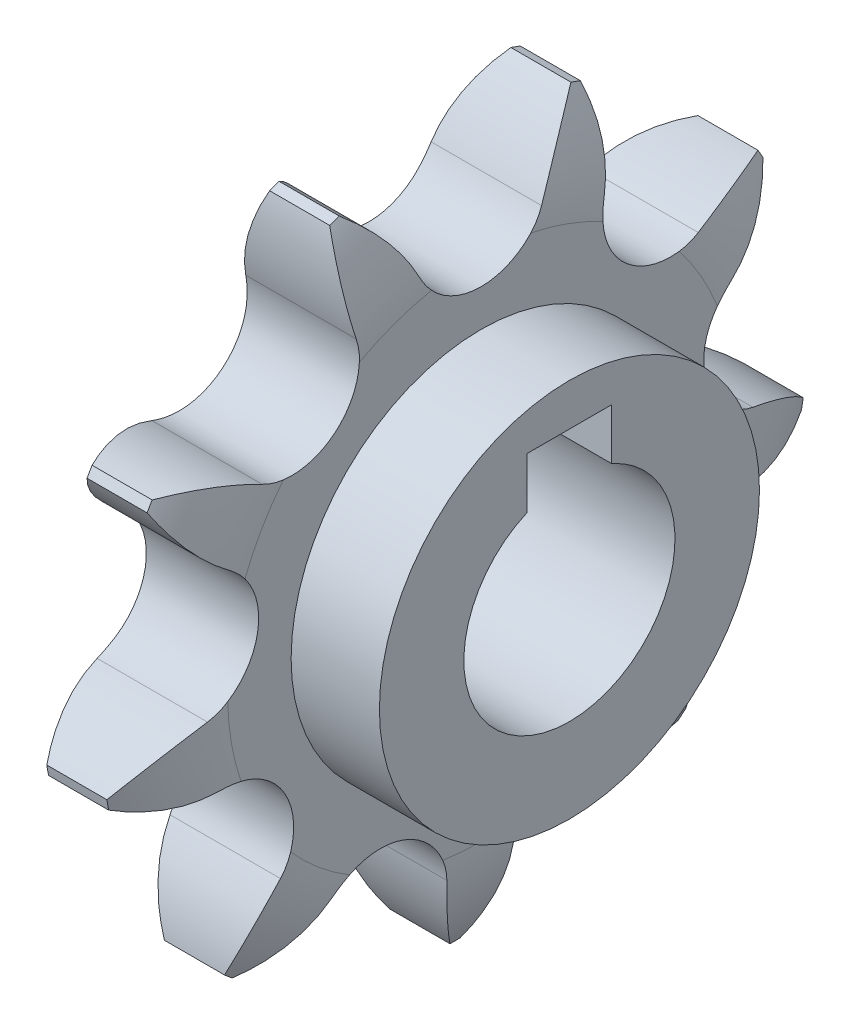
SolidWorks part; units mm, degrees
ref_plane "Plane1" through (0, 0, 0) normal (0, 0, 1) x (1, 0, 0)
ref_plane "Plane2" through (0, 0, 0) normal (0, 1, 0) x (1, 0, 0)
ref_plane "Plane3" through (0, 0, 0) normal (1, 0, 0) x (0, 0, -1)
sketch "Clipboard" plane through (0, 0, 0) normal (0, 1, 0) x (1, 0, 0)
  line L0 (0, 0) -> (9.4077, -1.49)
  line L1 (-15, 0) -> (100, 0) construction
  line L2 (0, 0) -> (-0.8203, 0.9272)
  line L3 (0, 0) -> (-8.8973, 3.4006)
  line L4 (0, 0) -> (3.0618, 0.4849)
  line L5 (0, 0) -> (-46.8476, -17.4728)
  line L6 (0, 0) -> (-4.4098, -2.9753)
  line L7 (-0.8203, 0.9272) -> (48.4205, 9.6097)
  line L8 (-76.2, 38.1) -> (-74.4, 38.1)
  line L9 (-73.3242, 40.7328) -> (-72.926, 40.7699)
  line L10 (-73.4529, 9.1872) -> (-63.2129, 9.1872)
  circle A0 centre (0, 0) radius 3.175
  circle A1 centre (0, 0) radius 8.4097
  circle A2 centre (0, 0) radius 37.5
  dimension "Num_teeth" = 9
  dimension "Thickness" = 5.3196
sketch "BasProSke" plane through (0, 0, 0) normal (0, 1, 0) x (1, 0, 0)
  line L0 (-10, 0) -> (60, 0) construction
  line L1 (0, 0) -> (0, 12.0069)
  line L2 (0, 0) -> (5.3196, 0)
  line L3 (5.3196, 0) -> (5.3196, 12.0069)
  line L4 (4.0816, 16.7027) -> (1.238, 16.7027)
  arc A0 (0, 12.0069) -> (1.238, 16.7027) centre (9.525, 12.0069) cw
  arc A1 (5.3196, 12.0069) -> (4.0816, 16.7027) centre (-4.2054, 12.0069) ccw
  dimension "D1" = 9.525
  dimension "Thickness" = 5.3196
  dimension "Diameter" = 33.4055
revolve "Base-Revolve" add sketch "BasProSke" angle 360 about L0
sketch "TooCutSke" plane through (0, 0, 0) normal (1, 0, 0) x (0, 0, -1)
  line L0 (0, 13.9564) -> (2.9063, 12.6011) construction
  line L1 (0, 0) -> (0, 107) construction
  line L2 (0, 13.9564) -> (-10, 13.9564) construction
  line L3 (0, 13.9564) -> (-2.9063, 12.6011) construction
  arc A0 (2.9063, 12.6011) -> (5.9941, 16.1247) centre (10.503, 9.0588) cw
  arc A1 (2.9063, 12.6011) -> (-2.9063, 12.6011) centre (0, 13.9564) cw
  arc A2 (-2.9063, 12.6011) -> (-5.9941, 16.1247) centre (-10.503, 9.0588) ccw
  arc A3 (5.9941, 16.1247) -> (-5.9941, 16.1247) centre (0, 0) ccw
extrude "ToothCut" cut sketch "TooCutSke" along normal through all
pattern_circular "TeethCuts" count 9 every 40 about axis through (-10, 0, 0) along (1, 0, 0) of "ToothCut"
sketch "HubNeaOneSke" plane through (0, 0, 0) normal (-1, 0, 0) x (0, 0, 1)
  circle A0 centre (0, 0) radius 8.4097
  dimension "Diameter" = 16.8193
extrude "HubNearOne" [suppressed] add sketch "HubNeaOneSke" along normal blind 44.6809
fillet "HubNearOneFillet" [suppressed] radius 0.4
sketch "HubNeaBotSke" plane through (0, 0, 0) normal (-1, 0, 0) x (0, 0, 1)
  circle A0 centre (0, 0) radius 8.4097
  dimension "Diameter" = 16.8193
extrude "HubNearBoth" [suppressed] add sketch "HubNeaBotSke" along normal blind 22.3405
fillet "HubNearBothFillet" [suppressed] radius 0.4
ref_plane "FarPln" through (5.3196, 0, 0) normal (1, 0, 0) x (0, 0, -1)
sketch "HubFarSke" plane through (5.3196, 0, 0) normal (1, 0, 0) x (0, 0, -1)
  circle A0 centre (0, 0) radius 8.4097
  dimension "Diameter" = 16.8193
extrude "HubFar" [suppressed] add sketch "HubFarSke" along normal blind 22.3405
fillet "HubFarFillet" [suppressed] radius 0.4
sketch "BorSke" plane through (0, 0, 0) normal (1, 0, 0) x (0, 0, -1)
  circle A0 centre (0, 0) radius 5
  dimension "Diameter" = 10
extrude "Bore" cut sketch "BorSke" along normal mid plane 100.001
sketch "KeySke" plane through (0, 0, 0) normal (1, 0, 0) x (0, 0, -1)
  line L0 (-2, 0) -> (-2, 6.8)
  line L1 (-2, 6.8) -> (2, 6.8)
  line L2 (2, 6.8) -> (2, 0)
  line L3 (0, 0) -> (0, 34) construction
  line L4 (-2, 0) -> (2, 0)
  dimension "Width" = 4
extrude "Keyway" [suppressed] cut sketch "KeySke" along normal mid plane 100.001
pattern_circular "Keyway2" [suppressed] count 2 every 90 about axis through (-10, 0, 0) along (1, 0, 0)
sketch "Sketch1" plane through (5.3196, 0, 0) normal (1, 0, 0) x (0, 0, -1)
  circle A0 centre (0, 0) radius 9
  circle A1 centre (0, 0) radius 3
  dimension "D1" = 18
  dimension "D2" = 6
extrude "Boss-Extrude1" add sketch "Sketch1" along normal offset from surface (16.6804 mm away) 22 up to face at (0, 0, -5)
sketch "Sketch2" plane through (0, 0, 0) normal (1, 0, 0) x (0, 0, -1)
  circle A0 centre (0, 0) radius 5
  dimension "D1" = 10
extrude "Cut-Extrude1" cut sketch "Sketch2" along normal blind 24
sketch "Sketch3" plane through (0, 0, 0) normal (-1, 0, 0) x (0, 0, 1)
  line L0 (-2, 7) -> (-2, 3)
  line L1 (-2, 7) -> (2, 7)
  line L2 (-2, 3) -> (2, 3)
  line L3 (2, 7) -> (2, 3)
  line L4 (-2, 7) -> (2, 3) construction
  line L5 (-2, 3) -> (2, 7) construction
  line L6 (0, 0) -> (0, 5) construction
  circle A0 centre (0, 0) radius 5 construction
  point P1 (0, 5)
  dimension "D1" = 4
  dimension "D2" = 4
extrude "Cut-Extrude2" cut sketch "Sketch3" against normal through all
sketch "Sketch4" plane through (22, 0, 0) normal (1, 0, 0) x (0, 0, -1)
  circle A0 centre (0, 0) radius 12.1759
extrude "Cut-Extrude3" cut sketch "Sketch4" against normal blind 12.5
equation "' \"Pitch@Clipboard\" = 12.7"
equation "' \"Num_strands@Clipboard\" = 1"
equation "' \"Num_teeth@Clipboard\" = 9"
equation "' \"Hub_dia@Clipboard\" = 50"
equation "' \"Overall_len@Clipboard\" = 3"
equation "' \"Diameter@BorSke\" = 12"
equation "' \"T_dim@Clipboard\" = 1"
equation "' \"Width@KeySke\" = 2"
equation "' \"Dr@Clipboard\" = 8.51"
equation "' \"Face_width@Clipboard\" = 7.2"
equation "' \"Side_radius@Clipboard\" = 12.7"
equation "' \"Side_relief@Clipboard\" = 1.27"
equation "' \"Transv_pitch@Clipboard\" = 13.92"
equation "' \"Show_teeth@Clipboard\" = 9"
equation "' \"Fillet_rad@Clipboard\" = 0.6"
equation "' \"Plate_wid@Clipboard\" = 11.8"
equation "\"Num_teeth@Clipboard\" = int( \"Num_teeth@Clipboard\" )"
equation "\"Num_teeth@Clipboard\" = ((sgn( \"Num_teeth@Clipboard\" - 5.0)+1)*( \"Num_teeth@Clipboard\" - 5.0))/2 +5.0"
equation "\"Num_teeth@Clipboard\" = ((sgn( \"Num_teeth@Clipboard\" - 200.0)-1)*( \"Num_teeth@Clipboard\" - 200.0))/-2 +200.0"
equation "\"MHD@Clipboard\" = \"Pitch@Clipboard\" * (1.0 / tan(3.14159265 / \"Num_teeth@Clipboard\" )) - 1.04 * \"Plate_wid@Clipboard\" - 0.76"
equation "\"Thickness@Clipboard\"  = \"Face_width@Clipboard\" + (\"Num_strands@Clipboard\" - 1) * \"Transv_pitch@Clipboard\""
equation "\"OAL@Clipboard\" = \"Thickness@Clipboard\" + 2 * \"Fillet_rad@Clipboard\" + 1"
equation "\"MHD@Clipboard\" = ((sgn( \"MHD@Clipboard\" - \"Hub_dia@Clipboard\" )-1)*( \"MHD@Clipboard\" - \"Hub_dia@Clipboard\" ))/-2+ \"Hub_dia@Clipboard\""
equation "\"OAL@Clipboard\" = ((sgn( \"OAL@Clipboard\" - \"Overall_len@Clipboard\" )+1)*( \"OAL@Clipboard\" - \"Overall_len@Clipboard\" ))/2 + \"Overall_len@Clipboard\" + 0.0005"
equation "\"Num_teeth@TeethCuts\" = int( \"Show_teeth@Clipboard\" ) + 1"
equation "\"Num_teeth@TeethCuts\" = ((sgn( \"Num_teeth@TeethCuts\" - \"Num_teeth@Clipboard\" )-1)*( \"Num_teeth@TeethCuts\" - \"Num_teeth@Clipboard\" ))/-2+ \"Num_teeth@Clipboard\""
equation "\"Num_teeth@TeethCuts\" = ((sgn( \"Num_teeth@TeethCuts\" - 2.0)+1)*( \"Num_teeth@TeethCuts\" - 2.0))/2 +2.0"
equation "\"Angle@TeethCuts\" = 360.0 / \"Num_teeth@Clipboard\""
equation "\"Seat_radius@TooCutSke\" = ( \"Pitch@Clipboard\" / 2.0) / sin(3.14159265 / \"Num_teeth@Clipboard\" ) - \"Dr@Clipboard\" / 2.0 + \"Dr@Clipboard\" * 0.505"
equation "\"R1@TooCutSke\"  = \"Dr@Clipboard\" * 0.505"
equation "\"X@TooCutSke\" = 140.0 - (90.0 / \"Num_teeth@Clipboard\")"
equation "\"R2@TooCutSke\" = 0.12 * \"Dr@Clipboard\" * ( \"Num_teeth@Clipboard\" + 2.0)"
equation "\"Overcut@TooCutSke\" = 0.5 + 0.625 * \"Pitch@Clipboard\" - 0.5 * \"Dr@Clipboard\"  +  \"Pitch@Clipboard\" / 2.0 / sin(3.14159265 / \"Num_teeth@Clipboard\" )"
equation "\"Diameter@BasProSke\" = 2.0 * ( 0.625 * \"Pitch@Clipboard\" - 0.5 * \"Dr@Clipboard\"  +  \"Pitch@Clipboard\" / 2.0 / sin(3.14159265 / \"Num_teeth@Clipboard\" ))"
equation "\"Thickness@BasProSke\"  = \"Thickness@Clipboard\""
equation "\"G1@BasProSke\" =  \"Side_relief@Clipboard\""
equation "\"G2@BasProSke\" =  \"Side_relief@Clipboard\""
equation "\"D1@BasProSke\" =  \"Side_radius@Clipboard\""
equation "\"Diameter@HubNeaOneSke\" = \"MHD@Clipboard\""
equation "\"Length@HubNearOne\" = \"OAL@Clipboard\" - \"Thickness@BasProSke\""
equation "\"Diameter@HubNeaBotSke\" = \"MHD@Clipboard\""
equation "\"Length@HubNearBoth\" = ( \"OAL@Clipboard\" - \"Thickness@BasProSke\" ) / 2.0"
equation "\"D1@HubNearOneFillet\" = \"Fillet_rad@Clipboard\""
equation "\"D1@HubNearBothFillet\" = \"Fillet_rad@Clipboard\""
equation "\"Thickness@FarPln\" = \"Thickness@BasProSke\""
equation "\"Diameter@HubFarSke\" = \"MHD@Clipboard\""
equation "\"Length@HubFar\" = ( \"OAL@Clipboard\" - \"Thickness@BasProSke\" ) / 2.0"
equation "\"D1@HubFarFillet\" = \"Fillet_rad@Clipboard\""
equation "\"D1@Bore\" = \"OAL@Clipboard\" * 2.0"
equation "\"D1@Keyway\" = \"OAL@Clipboard\" * 2.0"
equation "\"Offset@KeySke\" = \"T_dim@Clipboard\" + \"Diameter@BorSke\" / 2.0"
